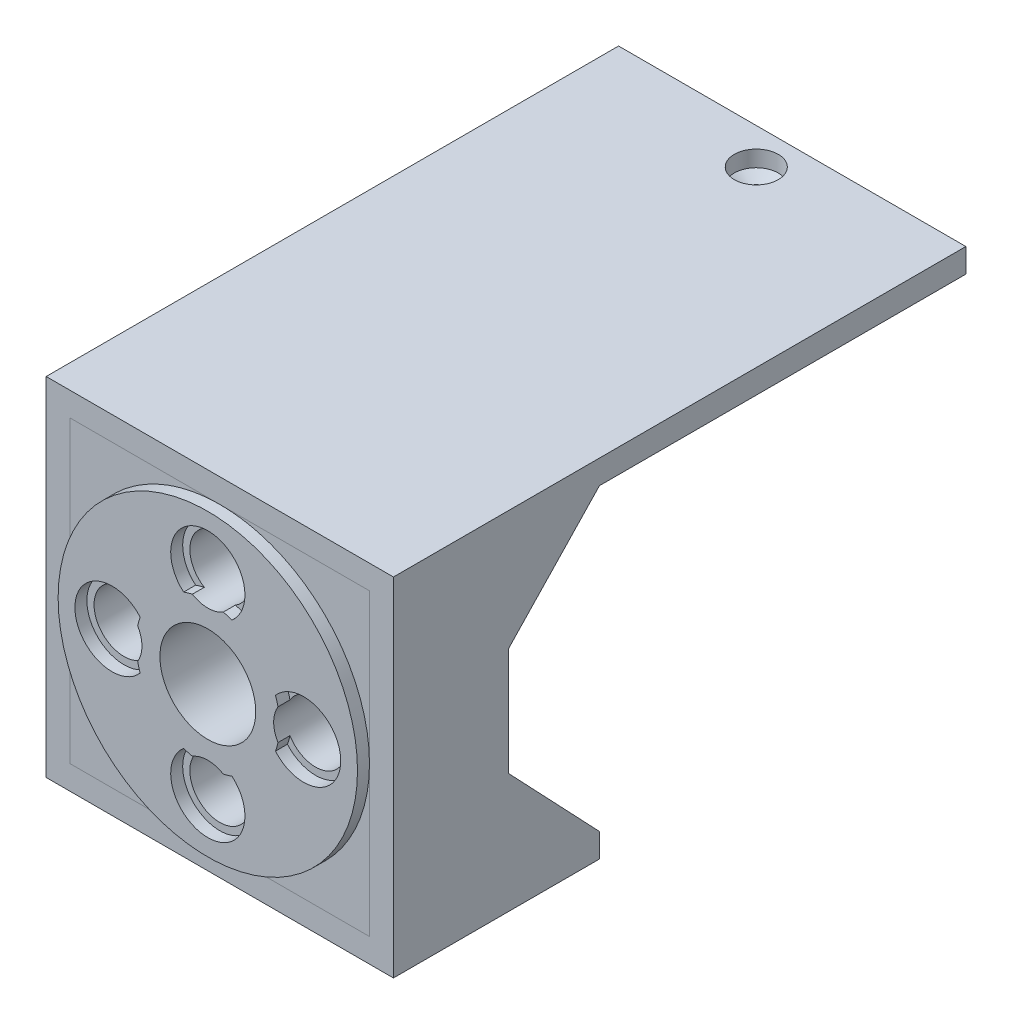
SolidWorks part; units mm, degrees
note: The reader was unsure of these and kept them because the rebuilt part matched: shared geometry of "草图3<3>", "草图3<4>", "草图3<6>", "草图5<5>", "草图5<7>".
ref_plane "前视基准面" through (0, 0, 0) normal (0, 0, 1) x (1, 0, 0)
ref_plane "上视基准面" through (0, 0, 0) normal (0, 1, 0) x (1, 0, 0)
ref_plane "右视基准面" through (0, 0, 0) normal (1, 0, 0) x (0, 0, -1)
other "Configuration Table"
sketch "草图3" plane through (0, 0, 0) normal (0, 0, 1) x (1, 0, 0)
  circle A0 centre (0, 0) radius 12.5
  circle A1 centre (0, 0) radius 4
  circle A2 centre (0, 8) radius 3.1
  circle A3 centre (0, 8) radius 2.5
  circle A4 centre (8, 0) radius 2.5
  circle A5 centre (8, 0) radius 3.1
  circle A6 centre (0, -8) radius 2.5
  circle A7 centre (0, -8) radius 3.1
  circle A8 centre (-8, 0) radius 2.5
  circle A9 centre (-8, 0) radius 3.1
  circle A10 centre (0, 0) radius 6
  point P19 (0, 0)
  dimension "D1" = 5
  dimension "D2" = 6.2
  dimension "D3" = 8
  dimension "D4" = 25
  dimension "D7" = 12
  dimension "D5" = 8
  dimension "D6" = 4
extrude "凸台-拉伸2" add sketch "草图3" against normal blind 7.8 contours A0 | A3 | A4 | A8 | A6 | A1
extrude "切除-拉伸1" cut sketch "草图3<3>" against normal blind 1 contours A2 A3 | A5 A4 | A9 A8 | A7 A6
sketch "草图3<3>" plane through (0, 0, 0) normal (0, 0, 1) x (1, 0, 0) same geometry as "草图3"
extrude "切除-拉伸2" cut sketch "草图3<4>" along normal blind 1 from surface at -7.8 contours A5 A4 | A7 A6 | A9 A8 | A2 A3
sketch "草图3<4>" plane through (0, 0, 0) normal (0, 0, 1) x (1, 0, 0) same geometry as "草图3"
extrude "凸台-拉伸3" add sketch "草图3<6>" against normal blind 2.8 from surface at -7.8 contours A0 A10 A5 A7 A9 A2
sketch "草图3<6>" plane through (0, 0, 0) normal (0, 0, 1) x (1, 0, 0) same geometry as "草图3"
sketch "草图5" plane through (0, 0, 0) normal (0, 0, 1) x (1, 0, 0)
  line L0 (-12.5, 12.5) -> (-14.5, 12.5)
  line L1 (12.5, -12.5) -> (-12.5, -12.5)
  line L2 (12.5, -12.5) -> (12.5, 12.5)
  line L3 (12.5, 12.5) -> (-12.5, 12.5)
  line L4 (-12.5, -12.5) -> (-12.5, 12.5)
  line L5 (14.5, -14.5) -> (-14.5, -14.5)
  line L6 (14.5, -14.5) -> (14.5, 14.5)
  line L7 (14.5, 14.5) -> (-14.5, 14.5)
  line L8 (-14.5, -14.5) -> (-14.5, 14.5)
  line L9 (12.5, 12.5) -> (14.5, 12.5)
  circle A0 centre (0, 0) radius 12.5 construction
  circle A1 centre (0, 0) radius 12.5
  circle M2 centre (0, 0) radius 12.5
  dimension "D1" = 2
  dimension "D2" = 2
  dimension "D3" = 2
  dimension "D4" = 2
extrude "凸台-拉伸4" add sketch "草图5" against normal blind 8 from offset 1 separate body contours L1 L2 M2 | L4 L1 M2 | L2 L3 M2 | L4 L3 M2 offset against normal yes
extrude "凸台-拉伸6" add sketch "草图5<5>" against normal blind 17.2 from offset 1 separate body contours L9 L2 L1 L4 L0 L8 L5 L6 | L3 L9 L6 L7 L8 L0 offset against normal yes
sketch "草图5<5>" plane through (0, 0, 0) normal (0, 0, 1) x (1, 0, 0) same geometry as "草图5"
extrude "凸台-拉伸13" add sketch "草图5<7>" against normal blind 30.6 from offset 18.2 contours L3 L9 L6 L7 L8 L0 offset against normal yes
sketch "草图5<7>" plane through (0, 0, 0) normal (0, 0, 1) x (1, 0, 0) same geometry as "草图5"
sketch "草图8" plane through (-14.5, 0, 0) normal (-1, 0, 0) x (0, 0, 1)
  line L0 (-10.6, -4.5) -> (-10.6, 4.5)
  line L1 (-10.6, 4.5) -> (-18.2, 12.5)
  line L2 (-18.2, 12.5) -> (-18.2, -12.5)
  line L3 (-18.2, -12.5) -> (-10.6, -4.5)
  line L4 (-48.8, 14.5) -> (-1, 14.5) construction
  line L5 (-18.2, -14.5) -> (-1, -14.5) construction
  line L7 (-48.8, 12.5) -> (-48.8, 14.5) construction
  dimension "D1" = 7.6
  dimension "D2" = 10
  dimension "D3" = 10
  dimension "D4" = 30.6
  dimension "D5" = 2
  dimension "D6" = 2
extrude "切除-拉伸3" cut sketch "草图8" against normal through all
sketch "草图9" plane through (0, -14.5, 0) normal (0, -1, 0) x (1, 0, 0)
  line L0 (-14.5, -18.2) -> (14.5, -18.2)
  line L1 (14.5, -18.2) -> (4.5, -10.6)
  line L2 (4.5, -10.6) -> (-4.5, -10.6)
  line L3 (-4.5, -10.6) -> (-14.5, -18.2)
  line L4 (14.5, -1) -> (-14.5, -1) construction
  line L6 (14.5, -18.2) -> (14.5, -1) construction
  line L8 (-14.5, -18.2) -> (-14.5, -1) construction
  dimension "D1" = 9
  dimension "D2" = 10
  dimension "D3" = 17.2
  dimension "D4" = 9.6
extrude "切除-拉伸4" cut sketch "草图9" against normal up to next
hole_wizard "孔1" positions "草图11" profile "草图10" legacy
sketch "草图11" plane through (0, 14.5, 0) normal (0, 1, 0) x (1, 0, 0)
  line L0 (0, 48.8) -> (0, 1) construction
  line L1 (14.5, 48.8) -> (-14.5, 48.8) construction
  line L2 (14.5, 1) -> (-14.5, 1) construction
  point P0 (0, 45.8)
  dimension "D1" = 3
sketch "草图10" plane through (0, 14.5, -45.8) normal (1, 0, 0) x (0, 0, 1)
  line L0 (0, 0) -> (0, 5.35)
  line L1 (0, 5.35) -> (0.9, 5.35)
  line L2 (0.9, 5.35) -> (0.9, 1.9118)
  line L3 (0.9, 1.9118) -> (1.835, 1.35)
  line L4 (1.835, 1.35) -> (1.835, 0)
  line L5 (1.835, 0) -> (0, 0)
  line L6 (0, -6.13) -> (0, 109.2824) construction
  line L7 (-0.9, 1.9118) -> (-1.835, 1.35) construction
  line L8 (0, 5.35) -> (-0.9, 5.35) construction
  dimension "直径" = 1.8
  dimension "深度" = 5.35
  dimension "沉头坑直径" = 3.67
  dimension "沉头坑深度" = 1.35
  dimension "导头角度" = 118
